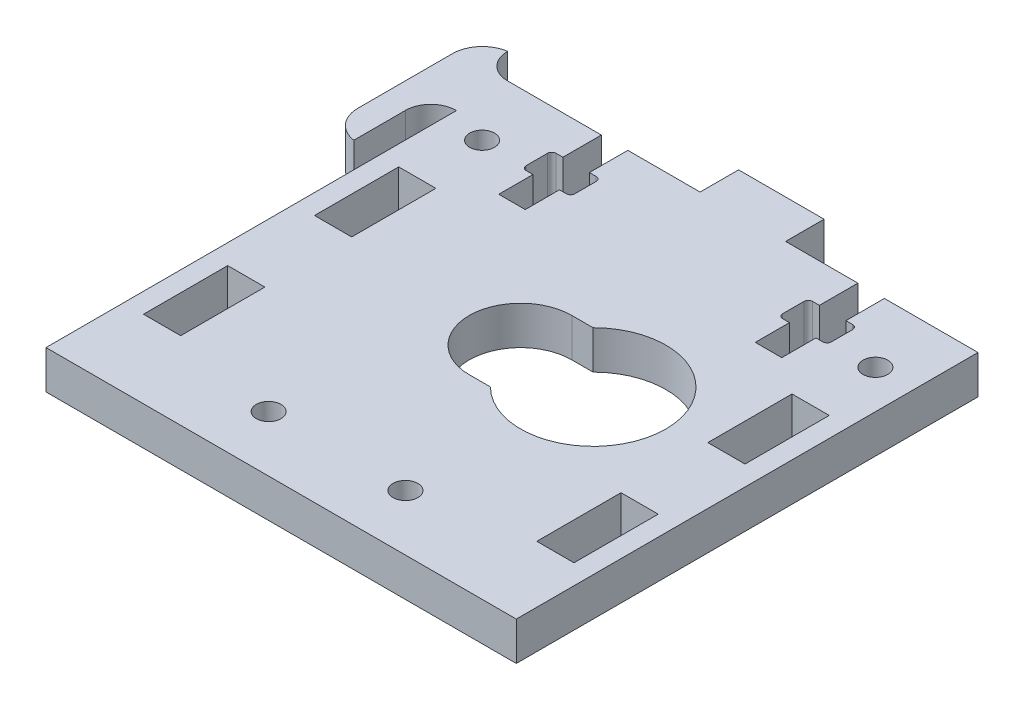
SolidWorks part; units mm, degrees
ref_plane "Front Plane" through (0, 0, 0) normal (0, 0, 1) x (1, 0, 0)
ref_plane "Top Plane" through (0, 0, 0) normal (0, 1, 0) x (1, 0, 0)
ref_plane "Right Plane" through (0, 0, 0) normal (1, 0, 0) x (0, 0, -1)
sketch "Sketch1" plane through (0, 0, 0) normal (0, 1, 0) x (1, 0, 0)
  line L1 (-27.5, 27) -> (27.5, 27)
  line L2 (-27.5, 27) -> (-27.5, -27)
  line L3 (-27.5, -27) -> (27.5, -27)
  line L4 (27.5, 27) -> (27.5, -27)
  line L5 (-27.5, 27) -> (27.5, -27) construction
  line L6 (-27.5, -27) -> (27.5, 27) construction
  point P0 (0, 0)
  dimension "D1" = 55
  dimension "D2" = 54
extrude "MainShape" add sketch "Sketch1" along normal blind 4.5
sketch "Sketch2" plane through (0, 4.5, 0) normal (0, 1, 0) x (1, 0, 0)
  line L0 (0, -27) -> (0, 27) construction
  line L1 (-27.5, -27) -> (27.5, -27) construction
  line L2 (27.5, 27) -> (-27.5, 27) construction
  line L4 (-5, 31.5) -> (5, 31.5)
  line L5 (-5, 31.5) -> (-5, 22.5)
  line L6 (-5, 22.5) -> (5, 22.5)
  line L7 (5, 31.5) -> (5, 22.5)
  line L8 (-5, 31.5) -> (5, 22.5) construction
  line L9 (-5, 22.5) -> (5, 31.5) construction
  dimension "D1" = 10
  dimension "D2" = 4.5
extrude "Tab1" add sketch "Sketch2" against normal through all
sketch "Sketch4" plane through (0, 4.5, 0) normal (0, 1, 0) x (1, 0, 0)
  line L0 (0, 31.5) -> (0, -27) construction
  line L1 (5, 31.5) -> (-5, 31.5) construction
  line L2 (-27.5, -27) -> (27.5, -27) construction
  line L3 (-15, 27) -> (-15, 15) construction
  line L4 (-5, 27) -> (-27.5, 27) construction
  line L5 (-13.45, 15) -> (-16.55, 15) construction
  line L6 (-16.55, 15) -> (-16.55, 27) construction
  line L7 (-13.45, 15) -> (-16.55, 15)
  line L8 (-16.55, 15) -> (-16.55, 19)
  line L9 (-16.55, 19) -> (-17.35, 19)
  line L10 (-17.85, 19.5) -> (-17.85, 22)
  line L11 (-17.35, 22.5) -> (-16.55, 22.5)
  line L12 (-16.55, 22.5) -> (-16.55, 27)
  line L13 (-16.55, 27) -> (-13.45, 27)
  line L14 (-13.45, 15) -> (-13.45, 27) construction
  line L15 (-13.45, 22.5) -> (-13.45, 27)
  line L16 (-12.65, 22.5) -> (-13.45, 22.5)
  line L17 (-12.15, 19.5) -> (-12.15, 22)
  line L18 (-13.45, 19) -> (-12.65, 19)
  line L19 (-13.45, 15) -> (-13.45, 19)
  line L20 (13.45, 15) -> (13.45, 27) construction
  line L21 (16.55, 15) -> (16.55, 27) construction
  line L22 (13.45, 15) -> (16.55, 15) construction
  line L23 (15, 27) -> (15, 15) construction
  line L24 (13.45, 15) -> (13.45, 19)
  line L25 (13.45, 19) -> (12.65, 19)
  line L26 (12.15, 19.5) -> (12.15, 22)
  line L27 (12.65, 22.5) -> (13.45, 22.5)
  line L28 (13.45, 22.5) -> (13.45, 27)
  line L29 (16.55, 27) -> (13.45, 27)
  line L30 (16.55, 22.5) -> (16.55, 27)
  line L31 (17.35, 22.5) -> (16.55, 22.5)
  line L32 (17.85, 19.5) -> (17.85, 22)
  line L33 (16.55, 19) -> (17.35, 19)
  line L34 (16.55, 15) -> (16.55, 19)
  line L35 (13.45, 15) -> (16.55, 15)
  arc A0 (-17.35, 19) -> (-17.85, 19.5) centre (-17.35, 19.5) cw
  arc A1 (-12.15, 19.5) -> (-12.65, 19) centre (-12.65, 19.5) cw
  arc A2 (-12.65, 22.5) -> (-12.15, 22) centre (-12.65, 22) cw
  arc A3 (-17.85, 22) -> (-17.35, 22.5) centre (-17.35, 22) cw
  arc A4 (17.85, 22) -> (17.35, 22.5) centre (17.35, 22) ccw
  arc A5 (12.65, 22.5) -> (12.15, 22) centre (12.65, 22) ccw
  arc A6 (12.15, 19.5) -> (12.65, 19) centre (12.65, 19.5) ccw
  arc A7 (17.35, 19) -> (17.85, 19.5) centre (17.35, 19.5) ccw
  point P24 (-17.85, 19)
  point P27 (-12.15, 19)
  point P30 (-12.15, 22.5)
  point P33 (-17.85, 22.5)
  point P56 (17.85, 22.5)
  point P57 (12.15, 22.5)
  point P58 (12.15, 19)
  point P59 (17.85, 19)
  dimension "D7" = 0.5
  dimension "D1" = 12
  dimension "D2" = 1.55
  dimension "D3" = 3.5
  dimension "D4" = 2.85
  dimension "D5" = 8
  dimension "D6" = 15
extrude "Cut-Extrude2" cut sketch "Sketch4" against normal through all
sketch "Sketch5" plane through (0, 4.5, 0) normal (0, 1, 0) x (1, 0, 0)
  line L0 (0, -27) -> (0, 31.5) construction
  line L1 (-27.5, -27) -> (27.5, -27) construction
  line L2 (5, 31.5) -> (-5, 31.5) construction
  line L3 (23, 27) -> (23, -27) construction
  line L4 (27.5, 27) -> (16.55, 27) construction
  line L5 (-23, 27) -> (-23, -27) construction
  line L6 (20.825, 11.925) -> (25.175, 11.925)
  line L7 (20.825, 11.925) -> (20.825, 2.075)
  line L8 (20.825, 2.075) -> (25.175, 2.075)
  line L9 (25.175, 11.925) -> (25.175, 2.075)
  line L10 (20.825, 11.925) -> (25.175, 2.075) construction
  line L11 (20.825, 2.075) -> (25.175, 11.925) construction
  line L12 (-20.825, 2.075) -> (-25.175, 11.925) construction
  line L13 (-20.825, 11.925) -> (-25.175, 2.075) construction
  line L14 (-25.175, 11.925) -> (-25.175, 2.075)
  line L15 (-20.825, 2.075) -> (-25.175, 2.075)
  line L16 (-20.825, 11.925) -> (-20.825, 2.075)
  line L17 (-20.825, 11.925) -> (-25.175, 11.925)
  line L18 (-27.5, -3) -> (27.5, -3) construction
  line L19 (-27.5, 27) -> (-27.5, -27) construction
  line L20 (27.5, -27) -> (27.5, 27) construction
  line L21 (-20.825, -17.925) -> (-25.175, -8.075) construction
  line L22 (-20.825, -8.075) -> (-25.175, -17.925) construction
  line L23 (20.825, -8.075) -> (25.175, -17.925) construction
  line L24 (20.825, -17.925) -> (25.175, -8.075) construction
  line L25 (-20.825, -17.925) -> (-25.175, -17.925)
  line L26 (-20.825, -17.925) -> (-20.825, -8.075)
  line L27 (-20.825, -8.075) -> (-25.175, -8.075)
  line L28 (-25.175, -17.925) -> (-25.175, -8.075)
  line L29 (25.175, -17.925) -> (25.175, -8.075)
  line L30 (20.825, -8.075) -> (25.175, -8.075)
  line L31 (20.825, -17.925) -> (20.825, -8.075)
  line L32 (20.825, -17.925) -> (25.175, -17.925)
  line L33 (-20.825, 11.925) -> (-25.175, 2.075) construction
  point P10 (23, 7)
  point P21 (-23, 7)
  point P36 (-23, -13)
  point P37 (23, -13)
  dimension "D1" = 23
  dimension "D2" = 9.85
  dimension "D3" = 4.35
  dimension "D4" = 20
  dimension "D5" = 20
extrude "Cut-Extrude3" cut sketch "Sketch5" against normal through all
sketch "Sketch6" plane through (0, 4.5, 0) normal (0, 1, 0) x (1, 0, 0)
  line L0 (0, -27) -> (0, 27) construction
  line L1 (5, 31.5) -> (-5, 31.5) construction
  line L3 (-27.5, 1) -> (27.5, 1) construction
  line L4 (-27.5, 27) -> (-27.5, -27) construction
  line L5 (27.5, -27) -> (27.5, 27) construction
  line L6 (27.5, 27) -> (16.55, 27) construction
  line L7 (-27.5, -27) -> (27.5, -27) construction
  line L9 (-27.5, 27) -> (27.5, 27) construction
  circle A0 centre (0, 1) radius 12
  point P4 (0, 31.5)
  dimension "D1" = 24
  dimension "D2" = 26
extrude "Cut-Extrude4" cut sketch "Sketch6" against normal through all
sketch "Sketch7" plane through (0, 4.5, 0) normal (0, 1, 0) x (1, 0, 0)
  line L0 (0, 1) -> (0, -27) construction
  line L3 (-27.5, -27) -> (27.5, -27) construction
  line L4 (8, -20.46) -> (-8, -20.46) construction
  circle A1 centre (-8, -20.46) radius 1.45
  circle A2 centre (8, -20.46) radius 1.45
  point P8 (0, -20.46)
  dimension "D1" = 2.9
  dimension "D3" = 21.46
extrude "Cut-Extrude5" [suppressed] cut sketch "Sketch7" against normal through all
sketch "Sketch8" plane through (0, 4.5, 0) normal (0, 1, 0) x (1, 0, 0)
  line L0 (-12, 1) -> (12, 1) construction
  line L1 (0, 1) -> (0, -20.46) construction
  line L2 (8, -20.46) -> (-8, -20.46) construction
  line L3 (0, -11) -> (0, 13) construction
  circle A0 centre (-8, -20.46) radius 1.45
  circle A1 centre (0, 1) radius 12 construction
  circle A2 centre (8, -20.46) radius 1.45
  dimension "D3" = 2.9
  dimension "D1" = 90
  dimension "D4" = 21.46
extrude "Cut-Extrude6" cut sketch "Sketch8" against normal through all
sketch "Sketch9" plane through (0, 4.5, 0) normal (0, 1, 0) x (1, 0, 0)
  line L0 (0, -27) -> (0, 31.5) construction
  line L1 (-27.5, -27) -> (27.5, -27) construction
  line L2 (5, 31.5) -> (-5, 31.5) construction
  line L3 (16, -27) -> (16, -16) construction
  line L4 (14.45, -16) -> (17.55, -16) construction
  line L5 (17.55, -16) -> (17.55, -27) construction
  line L6 (17.55, -27) -> (17.55, -22.5)
  line L7 (17.55, -22.5) -> (18.35, -22.5)
  line L8 (18.85, -22) -> (18.85, -19.5)
  line L9 (18.35, -19) -> (17.55, -19)
  line L10 (17.55, -19) -> (17.55, -16)
  line L11 (17.55, -16) -> (14.45, -16)
  line L12 (17.55, -27) -> (14.45, -27)
  line L13 (14.45, -16) -> (14.45, -27) construction
  line L14 (14.45, -19) -> (14.45, -16)
  line L15 (13.65, -19) -> (14.45, -19)
  line L16 (13.15, -22) -> (13.15, -19.5)
  line L17 (14.45, -22.5) -> (13.65, -22.5)
  line L18 (14.45, -27) -> (14.45, -22.5)
  line L19 (-14.45, -16) -> (-14.45, -27) construction
  line L20 (-17.55, -16) -> (-17.55, -27) construction
  line L21 (-14.45, -16) -> (-17.55, -16) construction
  line L22 (-16, -27) -> (-16, -16) construction
  line L23 (-14.45, -27) -> (-14.45, -22.5)
  line L24 (-14.45, -22.5) -> (-13.65, -22.5)
  line L25 (-13.15, -22) -> (-13.15, -19.5)
  line L26 (-13.65, -19) -> (-14.45, -19)
  line L27 (-14.45, -19) -> (-14.45, -16)
  line L28 (-17.55, -27) -> (-14.45, -27)
  line L29 (-17.55, -16) -> (-14.45, -16)
  line L30 (-17.55, -19) -> (-17.55, -16)
  line L31 (-18.35, -19) -> (-17.55, -19)
  line L32 (-18.85, -22) -> (-18.85, -19.5)
  line L33 (-17.55, -22.5) -> (-18.35, -22.5)
  line L34 (-17.55, -27) -> (-17.55, -22.5)
  arc A0 (18.35, -22.5) -> (18.85, -22) centre (18.35, -22) ccw
  arc A1 (18.85, -19.5) -> (18.35, -19) centre (18.35, -19.5) ccw
  arc A2 (13.15, -19.5) -> (13.65, -19) centre (13.65, -19.5) cw
  arc A3 (13.65, -22.5) -> (13.15, -22) centre (13.65, -22) cw
  arc A4 (-13.65, -22.5) -> (-13.15, -22) centre (-13.65, -22) ccw
  arc A5 (-13.15, -19.5) -> (-13.65, -19) centre (-13.65, -19.5) ccw
  arc A6 (-18.85, -19.5) -> (-18.35, -19) centre (-18.35, -19.5) cw
  arc A7 (-18.35, -22.5) -> (-18.85, -22) centre (-18.35, -22) cw
  point P16 (18.85, -22.5)
  point P19 (18.85, -19)
  point P30 (13.15, -19)
  point P31 (13.15, -22.5)
  point P54 (-13.15, -22.5)
  point P55 (-13.15, -19)
  point P56 (-18.85, -19)
  point P57 (-18.85, -22.5)
  dimension "D7" = 0.5
  dimension "D2" = 1.55
  dimension "D1" = 11
  dimension "D3" = 8
  dimension "D4" = 3.5
  dimension "D5" = 2.85
  dimension "D6" = 16
extrude "Cut-Extrude7" [suppressed] cut sketch "Sketch9" against normal through all
sketch "Sketch10" [suppressed] plane through (0, 0, 27) normal (0, 0, 1) x (1, 0, 0)
  line L0 (-27.5, 2.25) -> (27.5, 2.25) construction
  line L1 (-27.5, 4.5) -> (-27.5, 0) construction
  line L2 (27.5, 4.5) -> (27.5, 0) construction
  line L3 (-16, 4.5) -> (-16, 0) construction
  line L4 (-14.25, 4.5) -> (-17.75, 4.5) construction
  line L5 (16, 4.5) -> (16, 0) construction
  line L6 (17.75, 4.5) -> (14.25, 4.5) construction
  line L7 (17.75, 0) -> (14.25, 0) construction
  line L8 (-14.25, 0) -> (-17.75, 0) construction
  circle A0 centre (-16, 2.25) radius 1.6
  circle A1 centre (16, 2.25) radius 1.6
  dimension "D1" = 3.2
  dimension "D2" = 3.2
sketch "Sketch11" plane through (0, 4.5, 0) normal (0, 1, 0) x (1, 0, 0)
  line L0 (-20.825, 7) -> (-25.175, 7) construction
  line L1 (-20.825, 2.075) -> (-20.825, 11.925) construction
  line L2 (-25.175, 11.925) -> (-25.175, 2.075) construction
  line L3 (-23, 7) -> (-23, 27) construction
  line L4 (-16.55, 27) -> (-27.5, 27) construction
  line L5 (0, 31.5) -> (0, 0) construction
  line L6 (5, 31.5) -> (-5, 31.5) construction
  line L7 (23, 7) -> (23, 27) construction
  line L8 (20.825, 7) -> (25.175, 7) construction
  line L9 (-23, 7) -> (-23, 27) construction
  circle A0 centre (-23, 19.5) radius 1.45
  circle A1 centre (23, 19.5) radius 1.45
  dimension "D1" = 2.9
  dimension "D2" = 7.5
extrude "Cut-Extrude8" cut sketch "Sketch11" against normal through all
sketch "Sketch12" [suppressed] plane through (0, 4.5, 0) normal (0, 1, 0) x (1, 0, 0)
  line L0 (-27.5, -7) -> (-34, -17)
  line L1 (-27.5, 27) -> (-27.5, -27) construction
  line L2 (-34, -17) -> (-34, -27)
  line L3 (-34, -27) -> (-27.5, -27)
  line L4 (-27.5, -27) -> (-27.5, -7)
  line L5 (-27.5, -27) -> (27.5, -27) construction
  line L6 (0, -27) -> (0, 31.5) construction
  line L7 (5, 31.5) -> (-5, 31.5) construction
  line L8 (27.5, -27) -> (27.5, -7)
  line L9 (34, -27) -> (27.5, -27)
  line L10 (34, -17) -> (34, -27)
  line L11 (27.5, -7) -> (34, -17)
  point P4 (0, -27)
  dimension "D1" = 34
  dimension "D2" = 10
  dimension "D3" = 20
extrude "Boss-Extrude1" [suppressed] add sketch "Sketch12" against normal through all
sketch "Sketch14" [suppressed] plane through (0, 4.5, 0) normal (0, 1, 0) x (1, 0, 0)
  line L0 (-34, -27) -> (34, -27) construction
  line L2 (-34, -27) -> (34, -27) construction
  line L3 (0, -27) -> (0, 31.5) construction
  line L4 (5, 31.5) -> (-5, 31.5) construction
  line L6 (26.25, -16.5) -> (26.25, -27) construction
  line L8 (-28, -27) -> (-28, -16.5) construction
  line L9 (-26.25, -16.5) -> (-29.75, -16.5) construction
  line L10 (-29.75, -16.5) -> (-29.75, -27) construction
  line L11 (-26.25, -27) -> (-29.75, -27)
  line L12 (-29.75, -27) -> (-29.75, -23.2)
  line L13 (-29.75, -23.2) -> (-30.75, -23.2)
  line L14 (-31, -22.95) -> (-31, -19.25)
  line L15 (-30.75, -19) -> (-29.75, -19)
  line L16 (-29.75, -19) -> (-29.75, -16.5)
  line L17 (-29.75, -16.5) -> (-26.25, -16.5)
  line L18 (-26.25, -16.5) -> (-26.25, -27) construction
  line L19 (-26.25, -19) -> (-26.25, -16.5)
  line L20 (-25.25, -19) -> (-26.25, -19)
  line L21 (-25, -22.95) -> (-25, -19.25)
  line L22 (-26.25, -23.2) -> (-25.25, -23.2)
  line L23 (-26.25, -27) -> (-26.25, -23.2)
  line L24 (29.75, -16.5) -> (29.75, -27) construction
  line L25 (26.25, -16.5) -> (29.75, -16.5) construction
  line L26 (28, -27) -> (28, -16.5) construction
  line L27 (26.25, -27) -> (26.25, -23.2)
  line L28 (26.25, -23.2) -> (25.25, -23.2)
  line L29 (25, -22.95) -> (25, -19.25)
  line L30 (25.25, -19) -> (26.25, -19)
  line L31 (26.25, -19) -> (26.25, -16.5)
  line L32 (29.75, -16.5) -> (26.25, -16.5)
  line L33 (29.75, -19) -> (29.75, -16.5)
  line L34 (30.75, -19) -> (29.75, -19)
  line L35 (31, -22.95) -> (31, -19.25)
  line L36 (29.75, -23.2) -> (30.75, -23.2)
  line L37 (29.75, -27) -> (29.75, -23.2)
  line L38 (26.25, -27) -> (29.75, -27)
  line L39 (-26.25, -16.5) -> (-26.25, -27) construction
  arc A0 (-30.75, -23.2) -> (-31, -22.95) centre (-30.75, -22.95) cw
  arc A1 (-31, -19.25) -> (-30.75, -19) centre (-30.75, -19.25) cw
  arc A2 (-25, -19.25) -> (-25.25, -19) centre (-25.25, -19.25) ccw
  arc A3 (-25.25, -23.2) -> (-25, -22.95) centre (-25.25, -22.95) ccw
  arc A4 (25.25, -23.2) -> (25, -22.95) centre (25.25, -22.95) cw
  arc A5 (25, -19.25) -> (25.25, -19) centre (25.25, -19.25) cw
  arc A6 (31, -19.25) -> (30.75, -19) centre (30.75, -19.25) ccw
  arc A7 (30.75, -23.2) -> (31, -22.95) centre (30.75, -22.95) ccw
  point P2 (0, -27)
  dimension "D10" = 0.5
  dimension "D4" = 1.55
  dimension "D6" = 11
  dimension "D2" = 28
  dimension "D3" = 2.85
  dimension "D5" = 3.5
  dimension "D7" = 8
extrude "Cut-Extrude9" [suppressed] cut sketch "Sketch14" against normal through all
sketch "Sketch15" plane through (0, 4.5, 0) normal (0, 1, 0) x (1, 0, 0)
  circle A0 centre (0, 1) radius 12
  circle A1 centre (0, 1) radius 6
  circle A2 centre (0, 1) radius 12 construction
  dimension "D1" = 12
extrude "Boss-Extrude2" add sketch "Sketch15" against normal through all
sketch "Sketch16" plane through (0, 4.5, 0) normal (0, 1, 0) x (1, 0, 0)
  line L0 (0, 1) -> (27.5, 1) construction
  line L1 (27.5, -27) -> (27.5, 27) construction
  line L2 (0, 7) -> (2.4792, 7)
  line L3 (0, -5) -> (2.4792, -5)
  line L4 (0, 7) -> (0, -5)
  arc A0 (2.4792, -5) -> (2.4792, 7) centre (8.5, 1) ccw
  circle A1 centre (0, 1) radius 6 construction
  dimension "D1" = 17
  dimension "D2" = 8.5
extrude "Cut-Extrude10" cut sketch "Sketch16" against normal through all
sketch "Sketch17" plane through (0, 4.5, 0) normal (0, 1, 0) x (1, 0, 0)
  line L0 (-27.5, 22) -> (-27.5, 18) construction
  line L1 (-27.5, 27) -> (-27.5, -27) construction
  line L2 (-27.5, 25.5) -> (-27.5, 23.5)
  line L3 (-29, 22) -> (-29, 18)
  line L4 (-27.5, 22) -> (-27.5, 18) construction
  line L5 (-27.5, 16.5) -> (-27.5, 14.5)
  line L6 (-31, 22) -> (-31, 18)
  line L7 (-27.5, 25.5) -> (-27.5, 14.5) construction
  arc A0 (-27.5, 23.5) -> (-29, 22) centre (-27.5, 22) ccw
  arc A1 (-29, 18) -> (-27.5, 16.5) centre (-27.5, 18) ccw
  arc A2 (-27.5, 25.5) -> (-31, 22) centre (-27.5, 22) ccw
  arc A3 (-31, 18) -> (-27.5, 14.5) centre (-27.5, 18) ccw
  point P10 (-27.5, 20)
  dimension "D1" = 1.5
  dimension "D2" = 1.5
  dimension "D3" = 2
  dimension "D4" = 4
  dimension "D5" = 20
  dimension "D7" = 2
extrude "CableTieSlot" [suppressed] add sketch "Sketch17" against normal through all
sketch "Sketch18" plane through (0, 4.5, 0) normal (0, 1, 0) x (1, 0, 0)
  line L0 (-27.5, 27) -> (-27.55, 27)
  line L1 (-33.5, 30) -> (-33.5, 12)
  line L2 (-33.5, 12) -> (-30.5, 12)
  line L3 (-30.5, 12) -> (-30.5, 18.05)
  line L4 (-27.55, 21) -> (-27.5, 21)
  line L5 (-27.5, 27) -> (-27.5, -27) construction
  line L6 (-27.5, 21) -> (-27.5, 27)
  line L7 (-16.55, 27) -> (-27.5, 27) construction
  line L8 (-33.5, 30) -> (-30.5, 30)
  line L9 (-30.5, 30) -> (-30.5, 29.95)
  arc A0 (-27.55, 27) -> (-30.5, 29.95) centre (-27.55, 29.95) cw
  arc A1 (-30.5, 18.05) -> (-27.55, 21) centre (-27.55, 18.05) cw
  point P17 (-30.5, 27)
  dimension "D1" = 2.95
  dimension "D2" = 2.95
  dimension "D3" = 6
  dimension "D4" = 3
  dimension "D5" = 15
  dimension "D6" = 3
  dimension "D7" = 3
extrude "Boss-Extrude3" add sketch "Sketch18" against normal through all
fillet "Fillet1" radius 3.5 2 edges at (-33.5, 2.25, -30) (-33.5, 2.25, -12)
equation "\"X-ROD-SPACING\"=45"
equation "\"Y-ROD-SPACING\"=75"
equation "\"Z-ROD-SPACING\"=17.5"
equation "\"Y-BED-OFFSET\"=2"
equation "\"Y-BED-ROD-INSET\"=3.5"
equation "\"Y-BED-SCREW-SPACING\"=209"
equation "\"Y-BED-SCREW-CUTOUT-SLOT-HEIGHT\"=2"
equation "\"T-SLOT-NUT-FILLET-RADIUS\"=0.5"
equation "\"T-SLOT-SCREW-SHAFT-RADIUS\"=1.55"
equation "\"T-SLOT-SCREW-SHAFT-CUTOUT-LENGTH\"=11"
equation "\"T-SLOT-NUT-DEPTH\"=3.5"
equation "\"T-SLOT-NUT-WIDTH\"=2.85"
equation "\"T-SLOT-NUT-END-DISTANCE\"=8"
equation "\"ACRYLIC-THICKNESS\"=10"
equation "\"ACRYLIC-THICKNESS2\"=4.5"
equation "\"ACRYLIC-TAB-CUTOUT-SIZE\"=\"ACRYLIC-THICKNESS\"+\"ACRYLIC-TAB-TOLERANCE\"*2"
equation "\"ACRYLIC-TAB-WIDTH\"=\"ACRYLIC-THICKNESS\""
equation "\"ACRYLIC-M3-HOLE\"=2.9"
equation "\"SMOOTHROD-CAP-SCREW-DISTANCE\"=20"
equation "\"FRAME-WIDTH-INNER\"=370"
equation "\"NEMA17-HOLE-SPACING\"=31"
equation "\"NEMA17-CENTRAL-CUTOUT\"=22.5"
equation "\"Z-BRACKET-REACH\"=57"
equation "\"Z-ROD-INSET\"=13.5"
equation "\"TOP-BRACKET-SPACING\"=40"
equation "\"SMOOTHROD-X-LENGTH\"=350"
equation "\"SMOOTHROD-Y-LENGTH\"=350"
equation "\"SMOOTHROD-Z-LENGTH\"=350"
equation "\"SMOOTHROD-TIGHTENING-HEADROOM\"=.25"
equation "\"LEADSCREW-Z-LENGTH\"=300"
equation "\"SCREW-LENGTH-FRAME\"=\"ACRYLIC-THICKNESS\" + 10"
equation "\"SCREW-LENGTH-MOTOR\"=\"ACRYLIC-THICKNESS\" + 5"
equation "\"SCREW-LENGTH-EXTRUDER\"=28"
equation "\"SCREW-HEAD-RADIUS\"=6"
equation "\"PRINTED-X-SMOOTHROD-DIAMETER\"=8.8"
equation "\"PRINTED-X-SMOOTHROD-CUTOUT\"=10"
equation "\"PRINTED-X-BASE-HEIGHT\"=10"
equation "\"PRINTED-LM8UU-CUTOUT-SIZE\"=15.5"
equation "\"PRINTED-LM8UU-CUTOUT-LENGTH\"=24.5"
equation "\"PRINTED-X-IDLER-HEIGHT\"=16"
equation "\"PSU-MOUNTING-WIDTH\"=95"
equation "\"PSU-MOUNTING-HEIGHT\"=177"
equation "\"Y-BELT-TO-ROD-DISTANCE\"=20"
equation "\"SPOOL-HOLDER-ROD-SPACING\"=150"
equation "\"ACRYLIC-X-CARRIAGE-WIDTH\"=55"
equation "\"ACRYLIC-X-CARRIAGE-HEIGHT\"=75"
equation "\"ACRYLIC-X-CARRIAGE-SCREW-SPACING-X\"=15"
equation "\"ACRYLIC-X-CARRIAGE-SCREW-SPACING-Y\"=33"
equation "\"ACRYLIC-X-CARRIAGE-CENTER-TAB-SPACING\"=14"
equation "\"D1@Sketch1\"=\"ACRYLIC-X-CARRIAGE-WIDTH\""
equation "\"D1@MainShape\" = \"ACRYLIC-THICKNESS2\""
equation "\"D1@Sketch2\"=\"ACRYLIC-TAB-WIDTH\""
equation "\"D2@Sketch2\"=\"ACRYLIC-THICKNESS2\""
equation "\"D1@Sketch4\"=\"T-SLOT-SCREW-SHAFT-CUTOUT-LENGTH\"+1"
equation "\"D2@Sketch4\"=\"T-SLOT-SCREW-SHAFT-RADIUS\""
equation "\"D3@Sketch4\"=\"T-SLOT-NUT-DEPTH\""
equation "\"D4@Sketch4\"=\"T-SLOT-NUT-WIDTH\""
equation "\"D5@Sketch4\"=\"T-SLOT-NUT-END-DISTANCE\""
equation "\"D6@Sketch4\"=\"ACRYLIC-X-CARRIAGE-SCREW-SPACING-X\""
equation "\"D7@Sketch4\"=\"T-SLOT-NUT-FILLET-RADIUS\""
equation "\"ACRYLIC-X-CARRIAGE-EXTRUDER-SHELF-DEPTH\"=\"ACRYLIC-X-CARRIAGE-EXTRUDER-OFFSET\" + 28"
equation "\"D2@Sketch1\"=\"ACRYLIC-X-CARRIAGE-EXTRUDER-SHELF-DEPTH\""
equation "\"ACRYLIC-X-CARRIAGE-LM8UU-CUTOUT-WIDTH\"=24.25"
equation "\"ACRYLIC-X-CARRIAGE-EXTRUDER-BRACE-SPACING\"=23"
equation "\"ACRYLIC-X-CARRIAGE-EXTRUDER-BRACE-TAB-OFFSET\"=20"
equation "\"ACRYLIC-X-CARRIAGE-EXTRUDER-BRACE-HEIGHT\"=35"
equation "\"ACRYLIC-X-CARRIAGE-EXTRUDER-BRACE-SCREW-SPACING\"=22"
equation "\"D1@Sketch5\"=\"ACRYLIC-X-CARRIAGE-EXTRUDER-BRACE-SPACING\""
equation "\"D2@Sketch5\"=\"ACRYLIC-TAB-WIDTH\"-\"KERF\"*2"
equation "\"D3@Sketch5\"=\"ACRYLIC-THICKNESS2\"-\"KERF\"*2"
equation "\"D4@Sketch5\"=\"ACRYLIC-X-CARRIAGE-EXTRUDER-BRACE-TAB-OFFSET\""
equation "\"D1@Sketch7\"=\"ACRYLIC-M3-HOLE\""
equation "\"D3@Sketch8\"=\"ACRYLIC-M3-HOLE\""
equation "\"ACRYLIC-X-CARRIAGE-EXTRUDER-ANGLE\"=90"
equation "\"D1@Sketch8\"=\"ACRYLIC-X-CARRIAGE-EXTRUDER-ANGLE\""
equation "\"ACRYLIC-X-CARRIAGE-EXTRUDER-OFFSET\"=26"
equation "\"D2@Sketch6\"=\"ACRYLIC-X-CARRIAGE-EXTRUDER-OFFSET\""
equation "\"D1@Sketch9\"=\"T-SLOT-SCREW-SHAFT-CUTOUT-LENGTH\""
equation "\"D2@Sketch9\"=\"T-SLOT-SCREW-SHAFT-RADIUS\""
equation "\"D3@Sketch9\"=\"T-SLOT-NUT-END-DISTANCE\""
equation "\"D4@Sketch9\"=\"T-SLOT-NUT-DEPTH\""
equation "\"D5@Sketch9\"=\"T-SLOT-NUT-WIDTH\""
equation "\"D7@Sketch9\"=\"T-SLOT-NUT-FILLET-RADIUS\""
equation "\"ACRYLIC-TAB-TOLERANCE\"=-.05"
equation "\"D1@Sketch11\"=\"ACRYLIC-M3-HOLE\""
equation "\"D6@Sketch14\"=\"T-SLOT-SCREW-SHAFT-CUTOUT-LENGTH\""
equation "\"D3@Sketch14\"=\"T-SLOT-NUT-WIDTH\""
equation "\"D5@Sketch14\"=\"T-SLOT-NUT-DEPTH\""
equation "\"D4@Sketch14\"=\"T-SLOT-SCREW-SHAFT-RADIUS\""
equation "\"D10@Sketch14\"=\"T-SLOT-NUT-FILLET-RADIUS\""
equation "\"D7@Sketch14\"=\"T-SLOT-NUT-END-DISTANCE\""
equation "\"KERF\"=0.075"
equation "\"PRINTED-M3-HOLE\"=3.5"
equation "\"PRINTED-M3-NUT-AF\"=6.25"
equation "\"ACRYLIC-X-CARRIAGE-LM8UU-CUTOUT-HEIGHT\"=11.0"
equation "\"ACRYLIC-X-CARRIAGE-DUAL-WIDTH-MULTIPLIER\"=1.65"
equation "\"ACRYLIC-X-CARRIAGE-DUAL-HOTEND-SPACING\"=42"
equation "\"ACRYLIC-X-CARRIAGE-DUAL-WIDTH\"=75"
equation "\"ACRYLIC-X-CARRIAGE-DUAL-FAN-OFFSET\"=52"
equation "\"ACRYLIC-X-CARRIAGE-DUAL-FAN-HEIGHT\"=20"
equation "\"ACRYLIC-X-CARRIAGE-DUAL-HOTEND-SEPARATION\"=36"
equation "\"ACRYLIC-X-CARRIAGE-DUAL-MOUNT-PLATE-DEPTH\"=75"
equation "\"ACRYLIC-X-CARRIAGE-DUAL-MOUNT-BRACE-WIDTH\"=33"
equation "\"ACRYLIC-X-CARRIAGE-DUAL-MOUNT-SCREW-WIDTH\"=40"
equation "\"BLOWER-FAN-WIDTH\"=15"
